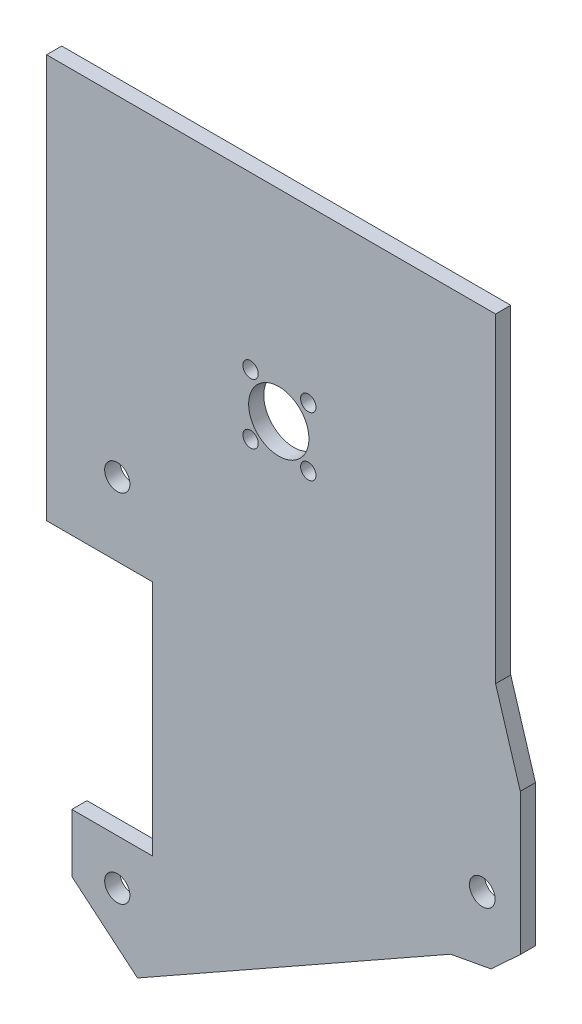
SolidWorks part; units mm, degrees
ref_plane "Front Plane" through (0, 0, 0) normal (0, 0, 1) x (1, 0, 0)
ref_plane "Top Plane" through (0, 0, 0) normal (0, 1, 0) x (1, 0, 0)
ref_plane "Right Plane" through (0, 0, 0) normal (1, 0, 0) x (0, 0, -1)
sketch "Sketch1" plane through (0, 0, 0) normal (0, 0, 1) x (1, 0, 0)
  line L0 (0, 0) -> (88.9, 0)
  line L1 (88.9, 0) -> (88.9, -3.5)
  line L2 (88.9, -3.5) -> (93.7917, -19.5)
  line L3 (93.7917, -19.5) -> (93.7917, -47.5)
  line L4 (0, 0) -> (0, -20)
  line L5 (0, -20) -> (21, -20)
  line L6 (21, -20) -> (21, -67)
  line L7 (21, -67) -> (5, -67)
  line L8 (5, -67) -> (5, -78.5)
  line L9 (5, -78.5) -> (18, -89.4083)
  line L10 (18, -89.4083) -> (80, -54.3304)
  line L11 (80, -54.3304) -> (88, -52.8477)
  line L12 (88, -52.8477) -> (93.7917, -47.5)
  dimension "D1" = 88.9
  dimension "D2" = 3.5
  dimension "D3" = 163
  dimension "D4" = 16
  dimension "D5" = 28
  dimension "D6" = 20
  dimension "D7" = 21
  dimension "D8" = 47
  dimension "D9" = 16
  dimension "D10" = 11.5
  dimension "D11" = 130
  dimension "D12" = 13
  dimension "D13" = 110.5
  dimension "D14" = 62
  dimension "D15" = 8
  dimension "D16" = 161
extrude "Boss-Extrude1" add sketch "Sketch1" along normal blind 3
sketch "Sketch2" plane through (0, 0, 0) normal (0, 1, 0) x (1, 0, 0)
  line L0 (45.8978, 14) -> (40.3978, 14) construction
  line L1 (0, -3) -> (88.9, -3)
  line L2 (0, -3) -> (0, 54)
  line L3 (0, 54) -> (88.9, 54)
  line L4 (88.9, -3) -> (88.9, 54)
  circle A0 centre (40.3978, 8.5) radius 1.5
  circle A1 centre (40.3978, 20) radius 1.5
  circle A2 centre (51.8978, 8.5) radius 1.5
  circle A3 centre (51.8978, 20) radius 1.5
  ellipse E0 centre (45.8978, 14) end of major axis (45.8978, 8) minor radius 5.5
  dimension "D9" = 3
  dimension "D10" = 3
  dimension "D11" = 3
  dimension "D12" = 3
  dimension "D1" = 88.9
  dimension "D2" = 57
  dimension "D3" = 45.8978
  dimension "D4" = 5.5
  dimension "D5" = 11.5
  dimension "D6" = 23
  dimension "D7" = 11.5
  dimension "D8" = 17
  dimension "D13" = 12
  dimension "D14" = 11
extrude "Boss-Extrude2" add sketch "Sketch2" along normal blind 3
ref_plane "Plane1" through (85.9, 0, 0) normal (1, 0, 0) x (0, 0, -1)
sketch "Sketch3" plane through (85.9, 0, 0) normal (1, 0, 0) x (0, 0, -1)
  line L0 (11.5, 0) -> (0, 0)
  line L1 (0, 0) -> (54, 0) construction
  line L2 (0, 0) -> (0, -11.5)
  line L3 (0, -19.5) -> (0, -3.5) construction
  line L4 (0, -11.5) -> (11.5, 0)
  dimension "D1" = 11.5
  dimension "D2" = 11.5
extrude "Boss-Extrude3" add sketch "Sketch3" against normal blind 84.5
sketch "Sketch4" plane through (0, 0, 0) normal (0, 0, -1) x (-1, 0, 0)
  line L0 (-1.4, -11.5) -> (-85.9, -11.5) construction
  line L1 (-81.4, -11.5) -> (-6.4, -11.5)
  line L2 (-81.4, -11.5) -> (-81.4, 0)
  line L3 (-81.4, 0) -> (-6.4, 0)
  line L4 (-6.4, -11.5) -> (-6.4, 0)
  line L5 (-50.8976, 0) -> (-85.9, 0) construction
  line L6 (-85.9, 13.7659) -> (-85.9, -13.7659) construction
  dimension "D1" = 75
  dimension "D2" = 4.5
extrude "Cut-Extrude2" cut sketch "Sketch4" along normal blind 84.5
sketch "Sketch6" plane through (0, 0, 3) normal (0, 0, 1) x (1, 0, 0)
  line L0 (0, 3) -> (0, -20) construction
  line L1 (0, 3) -> (88.9, 3) construction
  circle A0 centre (14, -76) radius 2.5
  circle A1 centre (86.263, -40.5) radius 2.54
  circle A2 centre (14, -5.5) radius 2.5
  dimension "D1" = 5
  dimension "D2" = 5
  dimension "D3" = 5.08
  dimension "D4" = 14
  dimension "D5" = 8.5
  dimension "D6" = 70.5
  dimension "D7" = 14
  dimension "D8" = 43.5
  dimension "D9" = 72.263
extrude "Cut-Extrude3" cut sketch "Sketch6" against normal blind 84.5
sketch "Sketch7" plane through (0, 0, 0) normal (0, -1, 0) x (1, 0, 0)
  line L1 (88.9, -54) -> (0, -54)
  line L2 (88.9, -54) -> (88.9, 0)
  line L3 (88.9, 0) -> (0, 0)
  line L4 (0, -54) -> (0, 0)
extrude "Cut-Extrude4" cut sketch "Sketch7" against normal through all both and the other way through all
sketch "Sketch8" plane through (0, 0, 0) normal (0, 0, -1) x (-1, 0, 0)
  line L0 (-88.9, 3) -> (0, 3) construction
  line L1 (-88.9, 3) -> (0, 3)
  line L2 (-88.9, 3) -> (-88.9, 59.896)
  line L3 (-88.9, 59.896) -> (0, 59.896)
  line L4 (0, 3) -> (0, 59.896)
  line L5 (-45.974, 20.018) -> (-40.005, 20.018) construction
  circle A0 centre (-45.974, 20.018) radius 5.969
  circle A1 centre (-40.386, 26.114) radius 1.524
  circle A2 centre (-40.386, 14.176) radius 1.524
  circle A3 centre (-51.816, 26.114) radius 1.524
  circle A4 centre (-51.816, 14.43) radius 1.524
  dimension "D8" = 11.938
  dimension "D9" = 3.048
  dimension "D10" = 3.048
  dimension "D11" = 3.048
  dimension "D12" = 3.048
  dimension "D1" = 56.896
  dimension "D2" = 88.9
  dimension "D3" = 23.114
  dimension "D4" = 11.43
  dimension "D5" = 17.018
  dimension "D6" = 11.938
  dimension "D7" = 5.588
  dimension "D13" = 45.974
  dimension "D14" = 11.43
extrude "Boss-Extrude4" add sketch "Sketch8" against normal up to surface (3 mm away) up to face at (16.5, -76, 3)
